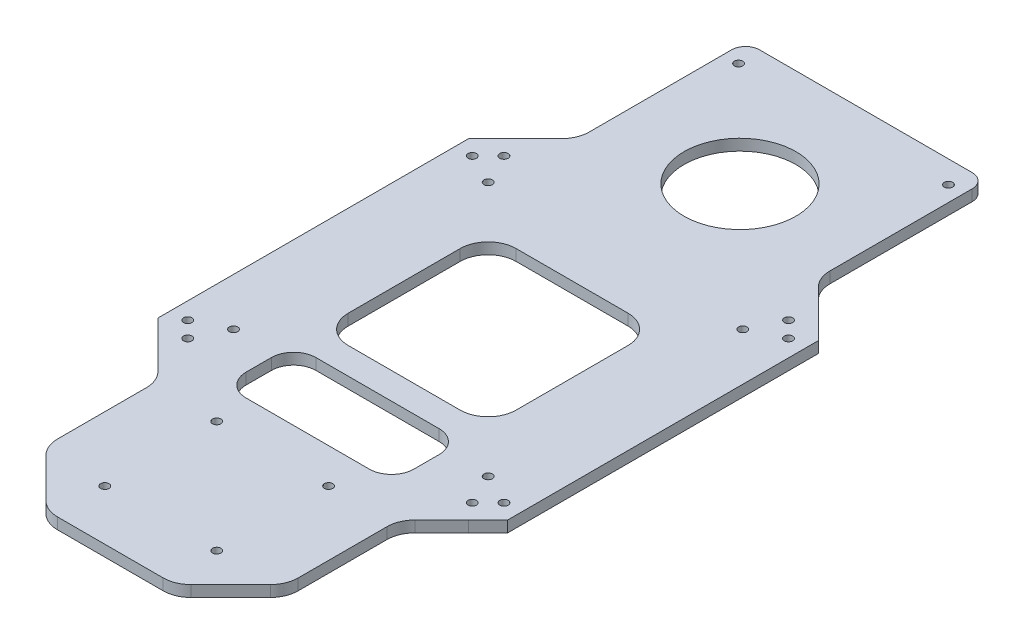
SolidWorks part; units mm, degrees
material "Thornel Mat VMA"
ref_plane "前视基准面" through (0, 0, 0) normal (0, 0, 1) x (1, 0, 0)
ref_plane "上视基准面" through (0, 0, 0) normal (0, 1, 0) x (1, 0, 0)
ref_plane "右视基准面" through (0, 0, 0) normal (1, 0, 0) x (0, 0, -1)
other "Configuration Table"
sketch "草图1" plane through (0, 0, 0) normal (0, 1, 0) x (1, 0, 0)
  line L0 (0, 0) -> (63.1315, 0) construction
  line L1 (-62.5, -62.5) -> (62.5, -62.5)
  line L2 (-62.5, -62.5) -> (-62.5, 62.5)
  line L3 (-62.5, 62.5) -> (62.5, 62.5)
  line L4 (62.5, -62.5) -> (62.5, 62.5)
  line L5 (-62.5, -62.5) -> (62.5, 62.5) construction
  line L6 (-62.5, 62.5) -> (62.5, -62.5) construction
  line L7 (0, 0) -> (0, 71.086) construction
  line L8 (50.8431, 56.5) -> (56.5, 50.8431) construction
  line L9 (43, 62.5) -> (43, 135)
  line L10 (43, 135) -> (-43, 135)
  line L11 (-43, 62.5) -> (-43, 135)
  line L12 (-43, -62.5) -> (-43, -135)
  line L13 (43, -135) -> (-43, -135)
  line L14 (43, -62.5) -> (43, -135)
  circle A4 centre (50.8431, 56.5) radius 1.5
  circle A5 centre (56.5, 50.8431) radius 1.5
  circle A6 centre (56.5, -50.8431) radius 1.5
  circle A7 centre (50.8431, -56.5) radius 1.5
  circle A8 centre (-50.8431, -56.5) radius 1.5
  circle A9 centre (-56.5, -50.8431) radius 1.5
  circle A10 centre (-56.5, 50.8431) radius 1.5
  circle A11 centre (-50.8431, 56.5) radius 1.5
  circle A12 centre (-37.5, 127) radius 1.5
  circle A13 centre (37.5, 127) radius 1.5
  point P0 (0, 0)
  point P14 (0, 135)
  point P42 (0, -135)
  dimension "D3" = 72.5
  dimension "D5" = 3
  dimension "D6" = 3
  dimension "D7" = 3
  dimension "D8" = 8
  dimension "D13" = 75
  dimension "D1" = 125
  dimension "D2" = 125
  dimension "D4" = 86
  dimension "D9" = 45
  dimension "D10" = 6
  dimension "D11" = 6
  dimension "D12" = 127
extrude "凸台-拉伸1" add sketch "草图1" along normal blind 4
chamfer "倒角1" distance 7 angle 45 4 edges at (-62.5, 2, 62.5) (-62.5, 2, -62.5) (62.5, 2, 62.5) (62.5, 2, -62.5)
sketch "草图3" plane through (0, 4, 0) normal (0, 1, 0) x (1, 0, 0)
  line L0 (0, 0) -> (95.6793, 0) construction
  line L1 (0, 0) -> (0, 105.8926) construction
  line L18 (-49.5, -49.5) -> (49.5, -49.5)
  line L19 (-49.5, -49.5) -> (-49.5, 49.5)
  line L20 (-49.5, 49.5) -> (49.5, 49.5)
  line L21 (49.5, -49.5) -> (49.5, 49.5)
  line L22 (-49.5, -49.5) -> (49.5, 49.5) construction
  line L23 (-49.5, 49.5) -> (49.5, -49.5) construction
  line L24 (-30, -30) -> (30, -30)
  line L25 (-30, -30) -> (-30, 30)
  line L26 (-30, 30) -> (30, 30)
  line L27 (30, -30) -> (30, 30)
  line L28 (-30, -30) -> (30, 30) construction
  line L29 (-30, 30) -> (30, -30) construction
  line L34 (0, -97) -> (73.0056, -97) construction
  line L36 (0, 0) -> (0, -149.5176) construction
  line L39 (-30, -39.5) -> (-30, -59.5)
  line L48 (-30, -39.5) -> (30, -39.5)
  line L49 (30, -39.5) -> (30, -59.5)
  line L50 (-30, -59.5) -> (30, -59.5)
  line L51 (-30, -59.5) -> (-30, -64.5)
  line L52 (-30, -64.5) -> (30, -64.5)
  line L53 (30, -64.5) -> (30, -59.5)
  circle A4 centre (-45.5, 45.5) radius 1.5
  circle A5 centre (45.5, 45.5) radius 1.5
  circle A6 centre (45.5, -45.5) radius 1.5
  circle A7 centre (-45.5, -45.5) radius 1.5
  circle A8 centre (0, 90) radius 20
  circle A9 centre (-20, -117) radius 1.5
  circle A10 centre (20, -117) radius 1.5
  circle A11 centre (20, -77) radius 1.5
  circle A12 centre (-20, -77) radius 1.5
  point P24 (-30, -49.5)
  point P26 (0, -59.5)
  point P30 (0, -39.5)
  dimension "D14" = 40
  dimension "D15" = 40
  dimension "D3" = 3
  dimension "D7" = 40
  dimension "D8" = 90
  dimension "D12" = 3
  dimension "D1" = 99
  dimension "D2" = 99
  dimension "D4" = 4
  dimension "D5" = 60
  dimension "D6" = 60
  dimension "D9" = 10
  dimension "D10" = 30
  dimension "D11" = 5
  dimension "D13" = 97
extrude "切除-拉伸1" cut sketch "草图3" against normal blind 4 contours L24 L27 L26 L25 | A4 | A5 | A6 | A7 | A8 | L49 L48 L39 L18 | L39 L50 L49 L18 | L52 L53 L50 L51 | A12 | A11 | A10 | A9
fillet "圆角3" radius 10 4 edges at (-30, 2, 30) (30, 2, 30) (30, 2, -30) (-30, 2, -30)
sketch "草图4" plane through (0, 4, 0) normal (0, 1, 0) x (1, 0, 0)
  line L0 (0, 0) -> (147.6965, 0) construction
  line L1 (0, 0) -> (0, 135.7677) construction
  line L2 (-50, 45) -> (70.2761, 45) construction
  line L7 (-50, 45) -> (-50, -77.0358) construction
  circle A0 centre (-41, 32.5) radius 1.5
  circle A1 centre (44, 30) radius 1.5
  circle A2 centre (-39, -27) radius 1.5
  circle A3 centre (39, -27) radius 1.5
  dimension "D1" = 3
  dimension "D3" = 12.5
  dimension "D5" = 3
  dimension "D8" = 3
  dimension "D10" = 3
  dimension "D12" = 72
  dimension "D2" = 9
  dimension "D4" = 94
  dimension "D6" = 15
  dimension "D7" = 11
  dimension "D9" = 72
  dimension "D11" = 89
  dimension "D13" = 50
  dimension "D14" = 45
fillet "圆角4" radius 5 2 edges at (43, 2, -135) (-43, 2, -135)
fillet "圆角5" radius 8 4 edges at (-30, 2, 64.5) (30, 2, 64.5) (30, 2, 39.5) (-30, 2, 39.5)
chamfer "倒角2" distance 12.5 angle 45 4 edges at (43, 2, -62.5) (-43, 2, -62.5) (43, 2, 62.5) (-43, 2, 62.5)
fillet "圆角6" radius 10 4 edges at (-43, 2, -75) (43, 2, -75) (43, 2, 75) (-43, 2, 75)
chamfer "倒角3" distance 20 angle 45 2 edges at (43, 2, 135) (-43, 2, 135)
fillet "圆角7" radius 10 4 edges at (43, 2, 115) (23, 2, 135) (-23, 2, 135) (-43, 2, 115)
